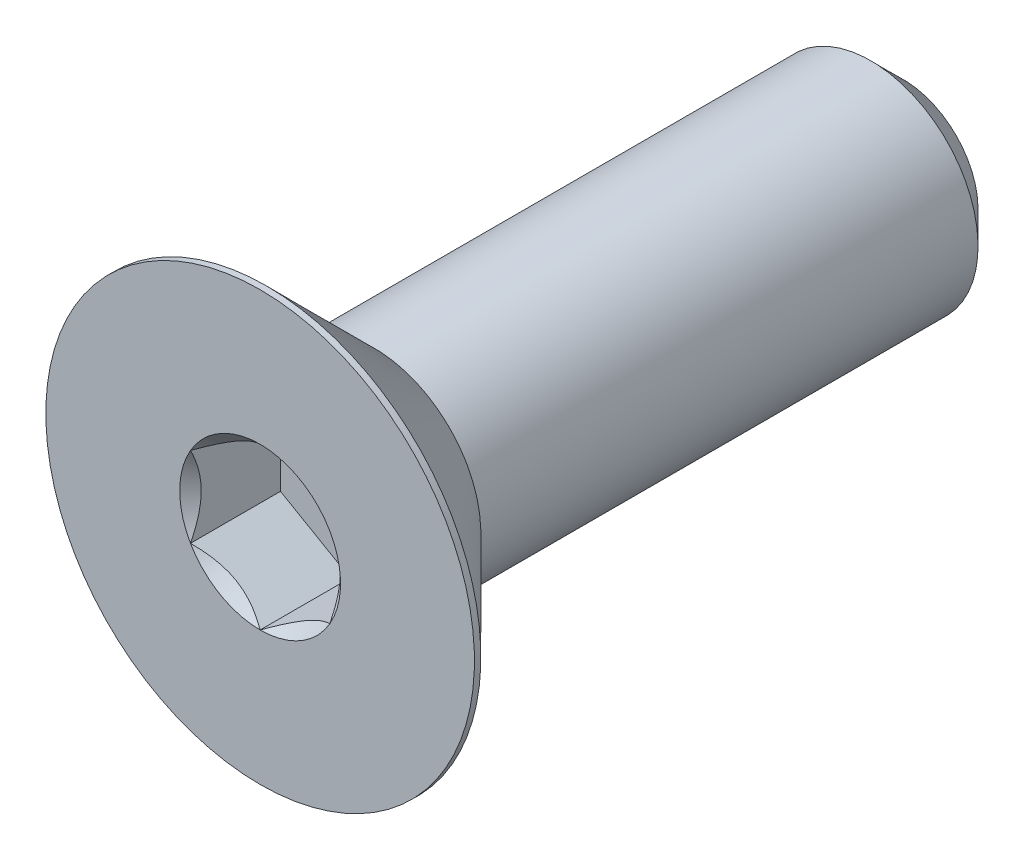
SolidWorks part; units mm, degrees
ref_plane "Front" through (0, 0, 0) normal (0, 0, 1) x (1, 0, 0)
ref_plane "Top" through (0, 0, 0) normal (0, 1, 0) x (1, 0, 0)
ref_plane "Right" through (0, 0, 0) normal (1, 0, 0) x (0, 0, -1)
sketch "Sketch11" plane through (0, 0, 0) normal (1, 0, 0) x (0, 0, -1)
  line L0 (-3, 2) -> (3, 2) construction
  line L5 (-3, 2) -> (-3, -2) construction
  line L6 (3, 1) -> (3, -1) construction
  line L7 (-2.99, 0.65) -> (-2.99, -0.65) construction
  line L8 (2.975, 1.0433) -> (3.375, 1.0433) construction
  line L9 (3.375, 1.0433) -> (3.175, 0.6969) construction
  line L10 (3.175, 0.6969) -> (2.975, 1.0433) construction
  line L11 (3.15, 0.7402) -> (3.2, 0.7402) construction
  line L12 (3.175, 0.7402) -> (3.175, 0.6969) construction
  line L13 (2.9875, 1.0217) -> (3.3625, 1.0217) construction
  line L14 (3.175, 1.0433) -> (3.175, 1) construction
  line L15 (3, 1) -> (3.35, 1) construction
  line L17 (-2.94, 2) -> (-0.94, 0) construction
  line L18 (-0.94, 0) -> (-2.94, -2) construction
  point P3 (-1.8, 2)
  point P8 (0, 2)
  point P21 (3.175, 1.0217)
  point P26 (-3, 0)
  point P28 (-2.99, 0)
  point P29 (3, 0)
  dimension "Length" = 6
  dimension "Head Diameter" = 4
  dimension "Thread Major Diameter" = 2
  dimension "Head Height" = 1.2
  dimension "Drive Size" = 1.3
  dimension "Thread Pitch" = 0.4
  dimension "D1" = 0.05
  dimension "D2" = 0.01
  dimension "D3" = 0.06
  dimension "Countersink Angle" = 90
sketch "Sketch1" plane through (0, 0, 0) normal (1, 0, 0) x (0, 0, -1)
  line L2 (-1.8, 1) -> (3, 1)
  line L3 (3, 1) -> (3, 0)
  line L4 (-2.16, 1) -> (-2.16, 0)
  line L5 (-1.8, 1) -> (-2.16, 1)
  line L6 (-3, 2) -> (-3, -2) construction
  line L7 (3, 1) -> (3, -1) construction
  line L8 (-2.16, 0) -> (3, 0)
  dimension "D1" = 0.84
revolve "Revolve1" add sketch "Sketch1" angle 360 mid plane about L8
chamfer "Chamfer1" distance 0.3 angle 45 1 edges at (0, -1, -3)
sketch "Sketch7" plane through (0, 0, 0) normal (1, 0, 0) x (0, 0, -1)
  line L2 (-3, 2) -> (-2.94, 2)
  line L5 (-1.8, 0.86) -> (-1.8, 0)
  line L6 (-3, 2) -> (-3, 0)
  line L8 (-3, 2) -> (-3, -2) construction
  line L9 (-3, 0) -> (-1.8, 0)
  line L12 (-2.94, 2) -> (-1.8, 0.86)
  line L13 (-2.94, 2) -> (-0.94, 0) construction
revolve "Revolve2" add sketch "Sketch7" angle 360 mid plane about L9 region at (0, 0.7698, 2.4817)
ref_plane "Plane1" through (0, 0, 1.8) normal (0, 0, 1) x (1, 0, 0)
sketch "Sketch5" plane through (0, 0, 3) normal (0, 0, 1) x (1, 0, 0)
  line L1 (0.65, -0.3753) -> (0.65, 0.3753)
  line L2 (0.65, 0.3753) -> (0, 0.7506)
  line L3 (0, 0.7506) -> (-0.65, 0.3753)
  line L4 (-0.65, 0.3753) -> (-0.65, -0.3753)
  line L5 (-0.65, -0.3753) -> (0, -0.7506)
  line L6 (0, -0.7506) -> (0.65, -0.3753)
  circle A0 centre (0, 0) radius 0.65 construction
extrude "Cut-Extrude2" cut sketch "Sketch5" against normal blind 0.84
sketch "Sketch6" plane through (0, 0, 3) normal (0, 0, -1) x (-1, 0, 0)
  circle A0 centre (0, 0) radius 0.7506
extrude "Cut-Extrude3" cut sketch "Sketch6" along normal blind 0.84 draft 45
sketch "Sketch12" [suppressed] plane through (0, 0, -3) normal (0, 0, -1) x (-1, 0, 0)
  circle A0 centre (0, 0) radius 1 construction
  circle A1 centre (0, 0) radius 1
curve "Helix/Spiral1" [suppressed] pitch 0.4 height 6 turns 15
sketch "Sketch13" [suppressed] plane through (0, 0, 0) normal (1, 0, 0) x (0, 0, -1)
  line L0 (2.9875, 1.0217) -> (3.3625, 1.0217)
  line L1 (3.3625, 1.0217) -> (3.2, 0.7402)
  line L2 (3.2, 0.7402) -> (3.15, 0.7402)
  line L3 (3.15, 0.7402) -> (2.9875, 1.0217)
sweep "Cut-Sweep1" [suppressed] cut profiles "Sketch13" path "Helix/Spiral1"
combine bodies "Combine1" [suppressed] operation type add bodies to combine 113 127
equation "\"D1@Chamfer1\"=\"Thread Pitch@Sketch11\" * .75"
equation "\"D1@Cut-Extrude2\"= \"Head Height@Sketch11\" * .7"
equation "\"D1@Cut-Extrude3\" = \"D1@Cut-Extrude2\""
equation "\"D1@Sketch11\"=\"Thread Pitch@Sketch11\"/8"
equation "\"D3@Sketch11\"=\"Head Height@Sketch11\"*.05"
equation "\"D4@Helix/Spiral1\"=\"Thread Pitch@Sketch11\""
equation "\"D1@Sketch1\"=\"Head Height@Sketch11\"*.7"
equation "\"D3@Helix/Spiral1\"=\"Length@Sketch11\""
